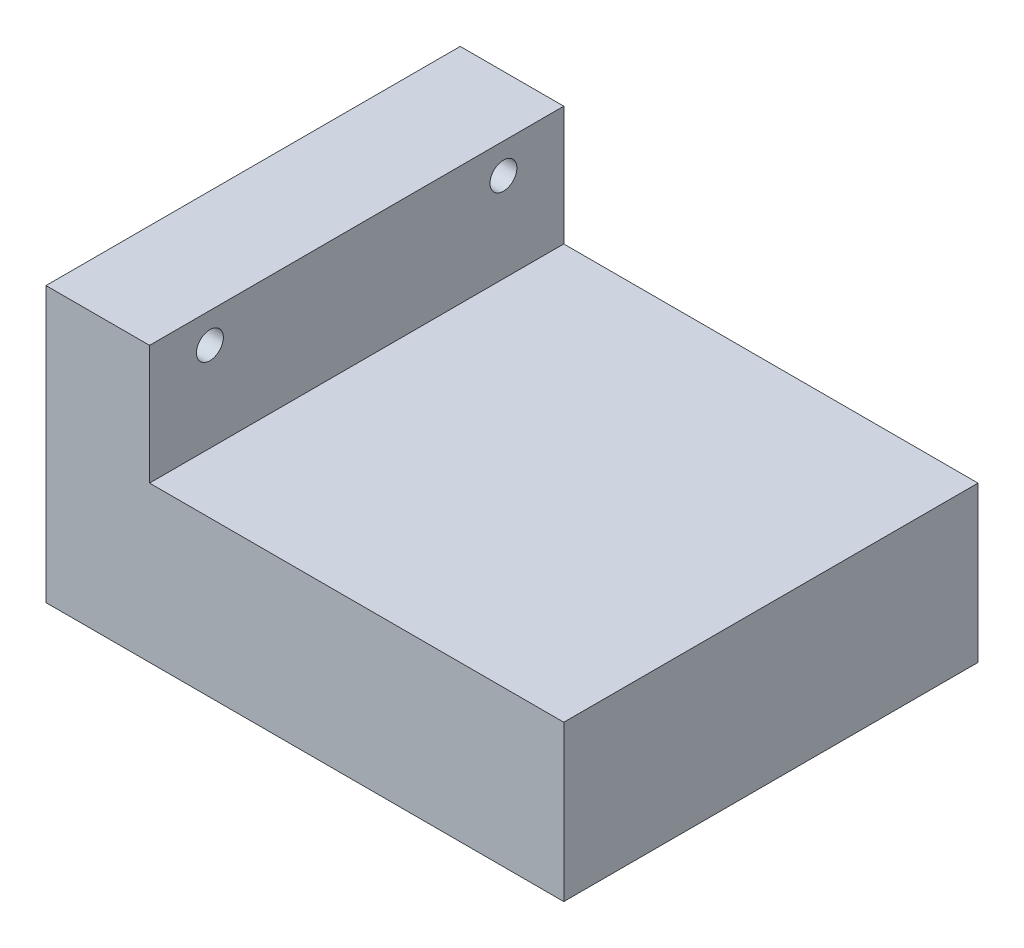
SolidWorks part; units mm, degrees
ref_plane "Front Plane" through (0, 0, 0) normal (0, 0, 1) x (1, 0, 0)
ref_plane "Top Plane" through (0, 0, 0) normal (0, 1, 0) x (1, 0, 0)
ref_plane "Right Plane" through (0, 0, 0) normal (1, 0, 0) x (0, 0, -1)
sketch "Sketch1" plane through (0, 0, 0) normal (0, 1, 0) x (1, 0, 0)
  line L0 (-19.05, 25.4) -> (-19.05, -25.4)
  line L1 (-31.75, 25.4) -> (31.75, 25.4)
  line L2 (-31.75, 25.4) -> (-31.75, -25.4)
  line L3 (-31.75, -25.4) -> (31.75, -25.4)
  line L4 (31.75, 25.4) -> (31.75, -25.4)
  line L5 (-31.75, 25.4) -> (31.75, -25.4) construction
  line L6 (-31.75, -25.4) -> (31.75, 25.4) construction
  point P0 (0, 0)
  dimension "D1" = 50.8
  dimension "D2" = 63.5
  dimension "D3" = 12.7
extrude "Boss-Extrude1" add sketch "Sketch1" along normal blind 19.05 contours L4 L1 L0 L3 region at (6.35, 0, 0)
extrude "Boss-Extrude2" add sketch "Sketch1<3>" along normal blind 33.6804 contours L2 L3 L0 L1 region at (-25.4, 0, 0)
sketch "Sketch1<3>" plane through (0, 0, 0) normal (0, 1, 0) x (1, 0, 0) same geometry as "Sketch1"
hole_wizard "M4x0.7 Tapped Hole1" positions "Sketch5" profile "Sketch4" tap size "M4x0.7" standard "ANSI Metric" end condition through all
sketch "Sketch5" plane through (-31.75, 0, 0) normal (-1, 0, 0) x (0, 0, 1)
  line L2 (-25.4, 33.6804) -> (25.4, 33.6804) construction
  line L7 (0, 33.6804) -> (0, 0) construction
  line L8 (-25.4, 0) -> (25.4, 0) construction
  point P0 (18, 30)
  point P29 (-18, 30)
  dimension "D1" = 30
  dimension "D2" = 36
sketch "Sketch4" plane through (-31.75, 30, 18) normal (0, 1, 0) x (0, 0, 1)
  line L0 (0, 0) -> (0, 63.5)
  line L1 (0, 63.5) -> (1.65, 63.5)
  line L2 (1.65, 63.5) -> (1.65, 0)
  line L5 (1.65, 0) -> (0, 0)
  line L11 (0, -6.35) -> (0, 107.95) construction
  dimension "Thread Major Dia." = 3.3
  dimension "Thru Tap Drill Depth" = 63.5
